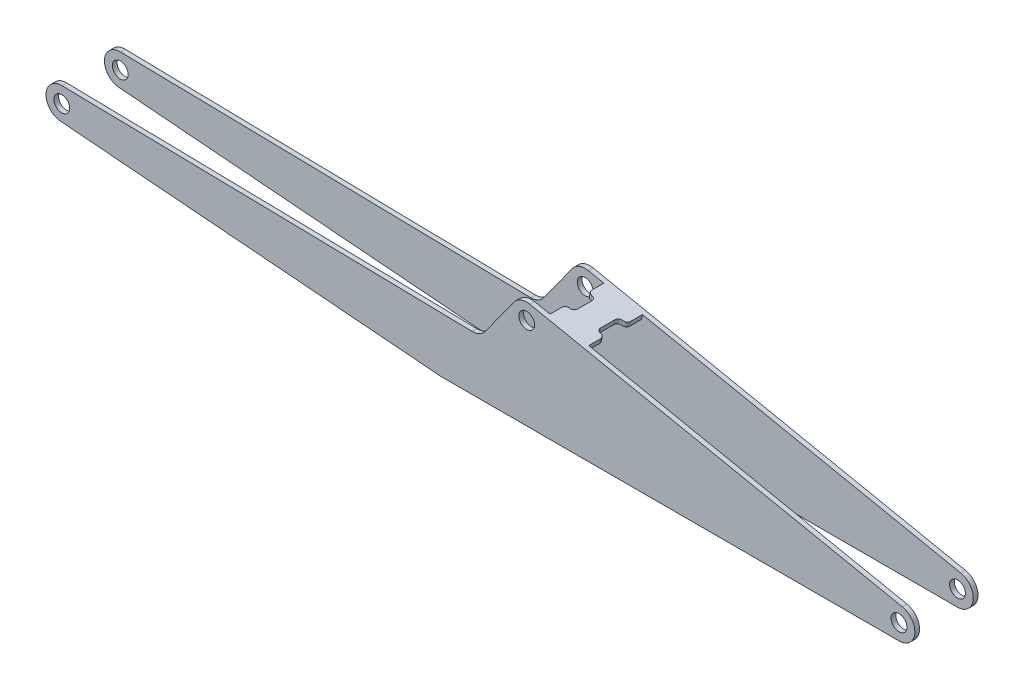
SolidWorks part; units mm, degrees
ref_plane "Front Plane" through (0, 0, 0) normal (0, 0, 1) x (1, 0, 0)
ref_plane "Top Plane" through (0, 0, 0) normal (0, 1, 0) x (1, 0, 0)
ref_plane "Right Plane" through (0, 0, 0) normal (1, 0, 0) x (0, 0, -1)
sketch "Profile Sketch" plane through (0, 0, 0) normal (0, 0, 1) x (1, 0, 0)
  line L0 (25, 34.4995) -> (-25, -34.4995) construction
  line L1 (-25, -34.4995) -> (-265.8209, -14.9656)
  line L2 (-264.8237, 4.9999) -> (0, 0)
  line L3 (25, 34.4995) -> (267.0422, -14.6999)
  line L4 (265.0502, -34.4995) -> (-25, -34.4995)
  line L5 (25, 34.4995) -> (0, 0)
  line L6 (-275, -4.4995) -> (-275, -34.4995) construction
  line L7 (-275, -34.4995) -> (-25, -34.4995) construction
  line L8 (25, 34.4995) -> (275, 34.4995) construction
  line L9 (275, 34.4995) -> (275, -25.5005) construction
  line L10 (25, 34.4995) -> (-25, 34.4995) construction
  line L11 (-25, 34.4995) -> (-25, -34.4995) construction
  arc A0 (-264.8237, 4.9999) -> (-265.8209, -14.9656) centre (-265.0125, -4.9984) ccw
  arc A1 (265.0502, -34.4995) -> (267.0422, -14.6999) centre (265.0502, -24.4995) ccw
  point P14 (-275, -4.4995)
  point P16 (275, -25.5005)
  dimension "D6" = 10
  dimension "D7" = 10
  dimension "D1" = 250
  dimension "D2" = 30
  dimension "D3" = 250
  dimension "D4" = 60
  dimension "D5" = 50
extrude "Profile Extrude" add sketch "Profile Sketch" along normal blind 40
fillet "Lightning Bolt Fillet" radius 10 3 edges at (-25, -34.4995, 20) (0, 0, 20) (25, 34.4995, 20)
sketch "Shell Sketch" plane through (-2.9435, -36.2886, 0) normal (-0.0808, -0.9967, 0) x (0.9967, -0.0808, 0)
  line L1 (-273.7408, 3) -> (276.1633, 3)
  line L2 (-273.7408, 3) -> (-273.7408, 37)
  line L3 (-273.7408, 37) -> (276.1633, 37)
  line L4 (276.1633, 3) -> (276.1633, 37)
  line L5 (-273.7408, 3) -> (276.1633, 37) construction
  line L6 (-273.7408, 37) -> (276.1633, 3) construction
  line L9 (-21.7254, 40) -> (266.9718, 40) construction
  line L10 (266.9718, 0) -> (276.1633, 0) construction
  line L13 (-273.7408, 40) -> (-273.7408, 0) construction
  point P0 (1.2112, 20)
  dimension "D1" = 3
  dimension "D2" = 3
extrude "Shell Cut" cut sketch "Shell Sketch" against normal up to surface (108.371 mm away) up to face at (149.1764, 9.2584, 20)
sketch "Holes Sketch" plane through (0, 0, 40) normal (0, 0, 1) x (1, 0, 0)
  line L0 (29.3187, 23.4171) -> (31.3107, 33.2167) construction
  line L1 (267.0422, -14.6999) -> (31.3107, 33.2167) construction
  line L2 (29.3187, 23.4171) -> (21.2213, 29.2849) construction
  line L3 (21.2213, 29.2849) -> (3.0645, 4.229) construction
  circle A0 centre (-265.0125, -4.9984) radius 5
  circle A1 centre (29.3187, 23.4171) radius 5
  circle A2 centre (265.0502, -24.4995) radius 5
  arc A3 (-264.8237, 4.9999) -> (-265.8209, -14.9656) centre (-265.0125, -4.9984) ccw construction
  arc A4 (265.0502, -34.4995) -> (267.0422, -14.6999) centre (265.0502, -24.4995) ccw construction
  dimension "D1" = 10
  dimension "D2" = 10
  dimension "D3" = 10
  dimension "D4" = 10
extrude "Holes Cut" cut sketch "Holes Sketch" against normal up to surface (40 mm away) up to face at (0.1028, -6.1261, 0)
sketch "Bowtie Support Sketch" plane through (7.7264, 38.0107, 0) normal (0.1992, 0.98, 0) x (0.98, -0.1992, 0)
  line L0 (39.0666, -27) -> (39.0666, -13)
  line L1 (34.0666, -37) -> (39.0666, -37)
  line L2 (34.0666, -37) -> (34.0666, -27)
  line L3 (34.0666, -27) -> (39.0666, -27)
  line L4 (39.0666, -37) -> (39.0666, -27) construction
  line L5 (34.0666, -37) -> (39.0666, -27) construction
  line L6 (34.0666, -27) -> (39.0666, -37) construction
  line L7 (34.0666, -13) -> (39.0666, -13)
  line L8 (34.0666, -13) -> (34.0666, -3)
  line L9 (34.0666, -3) -> (39.0666, -3)
  line L10 (39.0666, -13) -> (39.0666, -3) construction
  line L11 (34.0666, -13) -> (39.0666, -3) construction
  line L12 (34.0666, -3) -> (39.0666, -13) construction
  line L13 (39.0666, -37) -> (54.0666, -37)
  line L14 (39.0666, -37) -> (39.0666, -3) construction
  line L15 (39.0666, -3) -> (54.0666, -3)
  line L16 (54.0666, -37) -> (54.0666, -3) construction
  line L17 (39.0666, -37) -> (54.0666, -3) construction
  line L18 (39.0666, -3) -> (54.0666, -37) construction
  line L19 (54.0666, -37) -> (59.0666, -37)
  line L20 (54.0666, -37) -> (54.0666, -27) construction
  line L21 (54.0666, -27) -> (59.0666, -27)
  line L22 (59.0666, -37) -> (59.0666, -27)
  line L23 (54.0666, -37) -> (59.0666, -27) construction
  line L24 (54.0666, -27) -> (59.0666, -37) construction
  line L25 (54.0666, -13) -> (59.0666, -13)
  line L26 (54.0666, -13) -> (54.0666, -3) construction
  line L27 (54.0666, -3) -> (59.0666, -3)
  line L28 (59.0666, -13) -> (59.0666, -3)
  line L29 (54.0666, -13) -> (59.0666, -3) construction
  line L30 (54.0666, -3) -> (59.0666, -13) construction
  line L31 (54.0666, -27) -> (54.0666, -13)
  line L32 (24.0666, -37) -> (264.6188, -37) construction
  line L35 (264.6188, -3) -> (24.0666, -3) construction
  line L36 (24.0666, 0) -> (24.0666, -3) construction
  point P0 (36.5666, -32)
  point P5 (36.5666, -8)
  point P10 (46.5666, -20)
  point P15 (56.5666, -32)
  point P20 (56.5666, -8)
  dimension "D1" = 15
  dimension "D2" = 5
  dimension "D3" = 10
  dimension "D4" = 10
extrude "Bowtie Support Extrude" add sketch "Bowtie Support Sketch" against normal blind 3
fillet "Bowtie Support Fillet" radius 2.5 8 edges at (65.3105, 24.775, 13) (60.4107, 25.771, 13) (60.4107, 25.771, 27) (65.3105, 24.775, 27) (45.7113, 28.7589, 13) (45.7113, 28.7589, 27) (40.8115, 29.7549, 13) (40.8115, 29.7549, 27)
